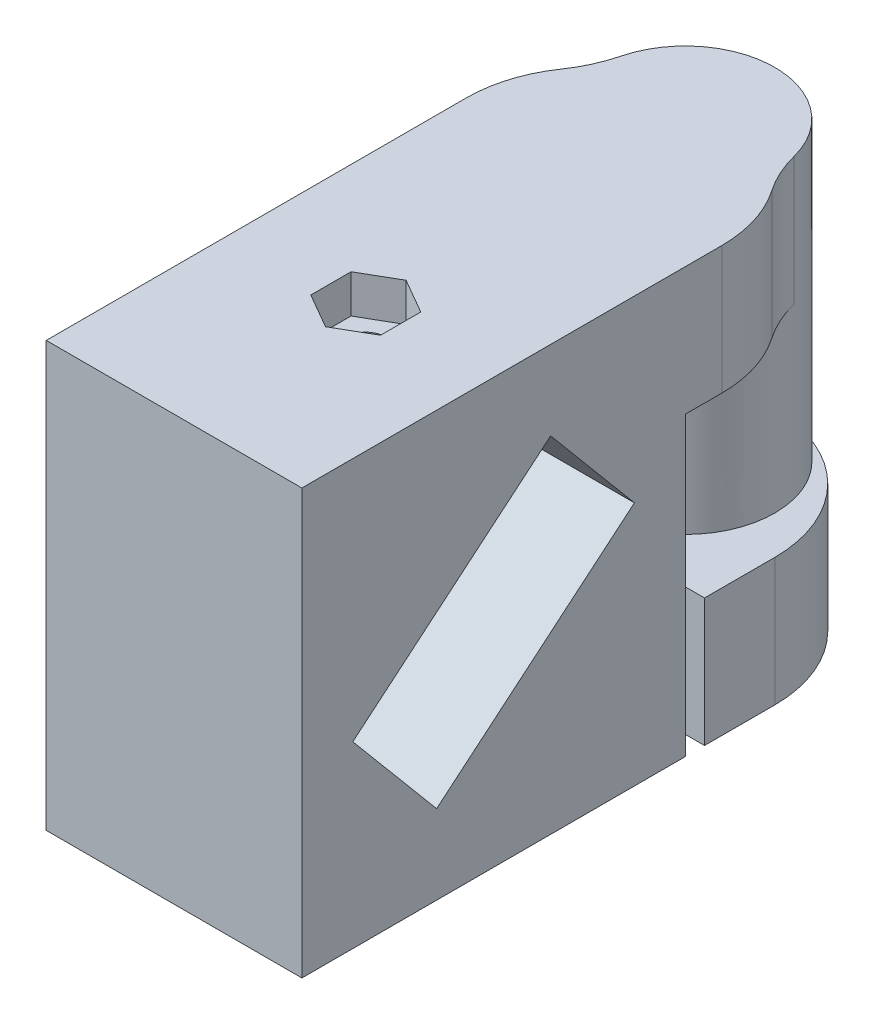
SolidWorks part; units mm, degrees
ref_plane "Спереди" through (0, 0, 0) normal (0, 0, 1) x (1, 0, 0)
ref_plane "Сверху" through (0, 0, 0) normal (0, 1, 0) x (1, 0, 0)
ref_plane "Справа" through (0, 0, 0) normal (1, 0, 0) x (0, 0, -1)
sketch "Эскиз1" plane through (0, 0, 0) normal (0, 1, 0) x (1, 0, 0)
  line L1 (-10, -15) -> (10, -15)
  line L2 (-10, -15) -> (-10, 15)
  line L3 (-10, 15) -> (10, 15)
  line L4 (10, -15) -> (10, 15)
  line L5 (-10, -15) -> (10, 15) construction
  line L6 (-10, 15) -> (10, -15) construction
  point P0 (0, 0)
  dimension "D1" = 20
  dimension "D2" = 30
extrude "Бобышка-Вытянуть1" add sketch "Эскиз1" along normal blind 33.2
sketch "Эскиз2" plane through (0, 33.2, 0) normal (0, 1, 0) x (1, 0, 0)
  line L0 (0, 15) -> (0, -15) construction
  line L1 (10, 15) -> (-10, 15) construction
  line L2 (-10, -15) -> (10, -15) construction
  circle A0 centre (0, 0) radius 1.5
  dimension "D1" = 3
extrude "Вырез-Вытянуть1" cut sketch "Эскиз2" against normal through all
sketch "Эскиз5" plane through (-10, 0, 0) normal (-1, 0, 0) x (0, 0, 1)
  line L0 (0, 33.2) -> (0, 0) construction
  line L2 (-15, 33.2) -> (15, 33.2) construction
  line L3 (15, 0) -> (-15, 33.2) construction
  line L4 (-4.4588, 26.999) -> (-11.0153, 19.1853)
  line L5 (-4.4588, 26.999) -> (11.0153, 14.0147)
  line L6 (11.0153, 14.0147) -> (4.4588, 6.201)
  line L7 (-11.0153, 19.1853) -> (4.4588, 6.201)
  line L8 (-4.4588, 26.999) -> (4.4588, 6.201) construction
  line L9 (11.0153, 14.0147) -> (-11.0153, 19.1853) construction
  point P5 (0, 16.6)
  point P6 (0, 16.6)
  dimension "D1" = 20.2
  dimension "D2" = 10.2
  dimension "D3" = 40
extrude "Вырез-Вытянуть4" cut sketch "Эскиз5" against normal blind 30
sketch "Sketch1" plane through (0, 0, -15) normal (0, 0, -1) x (-1, 0, 0)
  line L0 (0, 0) -> (0, 33.2) construction
  line L1 (-10, 0) -> (10, 0) construction
  line L2 (-10, 33.2) -> (10, 33.2) construction
  line L4 (-10, 23.2) -> (10, 23.2)
  line L5 (-10, 23.2) -> (-10, 33.2)
  line L6 (-10, 33.2) -> (10, 33.2)
  line L7 (10, 23.2) -> (10, 33.2)
  line L8 (-10, 23.2) -> (10, 33.2) construction
  line L9 (-10, 33.2) -> (10, 23.2) construction
  point P6 (0, 28.2)
  dimension "D1" = 10
extrude "Boss-Extrude2" add sketch "Sketch1" along normal blind 10
sketch "Sketch2" plane through (0, 23.2, 0) normal (0, -1, 0) x (1, 0, 0)
  line L0 (10, -25) -> (-10, -25) construction
  circle A0 centre (0, -25) radius 7
  dimension "D1" = 14
extrude "Boss-Extrude3" add sketch "Sketch2" along normal up to surface and the other way up to surface up to face at (0, 0, 1.5) other way up to face at (0, 33.2, 1.5)
fillet "Fillet1" radius 10 2 edges at (-10, 28.2, -25) (10, 28.2, -25)
sketch "Sketch3" plane through (0, 0, 0) normal (0, -1, 0) x (1, 0, 0)
  line L0 (10, -15) -> (-10, -15) construction
  line L1 (-10, -32) -> (10, -32)
  line L2 (-10, -32) -> (-10, -16.5)
  line L3 (-10, -16.5) -> (10, -16.5)
  line L4 (10, -32) -> (10, -16.5)
  line L5 (-10, -32) -> (10, -16.5) construction
  line L6 (-10, -16.5) -> (10, -32) construction
  line L7 (0, -15) -> (0, -32) construction
  circle A2 centre (0, -25) radius 7 construction
  point P0 (0, -24.25)
  dimension "D1" = 15.5
extrude "Boss-Extrude4" add sketch "Sketch3" against normal blind 10
fillet "Fillet2" radius 10 4 edges at (10, 5, -32) (-10, 5, -32) (7, 28.2, -25) (-7, 28.2, -25)
sketch "Sketch4" plane through (0, 0, 0) normal (0, -1, 0) x (1, 0, 0)
  circle A0 centre (0, 0) radius 3.15
  dimension "D1" = 6.3
extrude "Cut-Extrude1" cut sketch "Sketch4" against normal blind 3
sketch "Sketch5" plane through (0, 33.2, 0) normal (0, 1, 0) x (1, 0, 0)
  line L1 (0, 3.15) -> (-2.728, 1.575)
  line L2 (-2.728, 1.575) -> (-2.728, -1.575)
  line L3 (-2.728, -1.575) -> (0, -3.15)
  line L4 (0, -3.15) -> (2.728, -1.575)
  line L5 (2.728, -1.575) -> (2.728, 1.575)
  line L6 (2.728, 1.575) -> (0, 3.15)
  circle A0 centre (0, 0) radius 3.15 construction
extrude "Cut-Extrude2" cut sketch "Sketch5" against normal blind 3
